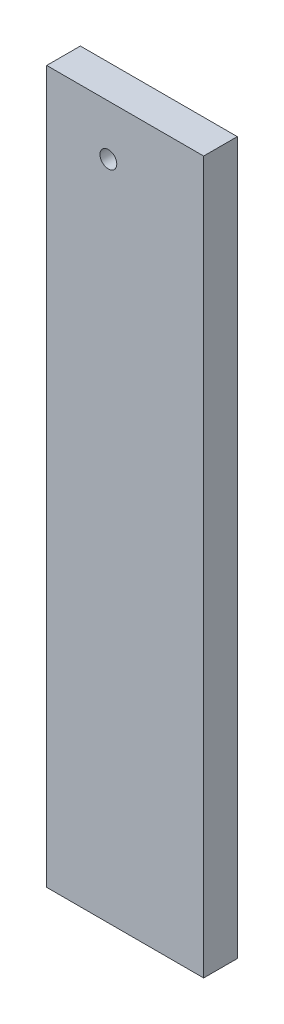
SolidWorks part; units mm, degrees
ref_plane "Front Plane" through (0, 0, 0) normal (0, 0, 1) x (1, 0, 0)
ref_plane "Top Plane" through (0, 0, 0) normal (0, 1, 0) x (1, 0, 0)
ref_plane "Right Plane" through (0, 0, 0) normal (1, 0, 0) x (0, 0, -1)
sketch "Sketch1" plane through (0, 0, 0) normal (0, 0, 1) x (1, 0, 0)
  line L1 (44.45, 201.6125) -> (-44.45, 201.6125)
  line L2 (44.45, 201.6125) -> (44.45, -201.6125)
  line L3 (44.45, -201.6125) -> (-44.45, -201.6125)
  line L4 (-44.45, 201.6125) -> (-44.45, -201.6125)
  line L5 (44.45, 201.6125) -> (-44.45, -201.6125) construction
  line L6 (44.45, -201.6125) -> (-44.45, 201.6125) construction
  point P0 (0, 0)
  dimension "D1" = 403.225
  dimension "D2" = 88.9
extrude "Boss-Extrude1" add sketch "Sketch1" along normal mid plane 19.05
sketch "Sketch2" plane through (0, 0, 9.525) normal (0, 0, 1) x (1, 0, 0)
  line L0 (44.45, -201.6125) -> (44.45, 201.6125) construction
  line L1 (44.45, 201.6125) -> (-44.45, 201.6125) construction
  circle A0 centre (-9.525, 173.0375) radius 4.7625
  dimension "D3" = 9.525
  dimension "D1" = 53.975
  dimension "D2" = 28.575
extrude "Cut-Extrude1" cut sketch "Sketch2" against normal through all both and the other way through all
